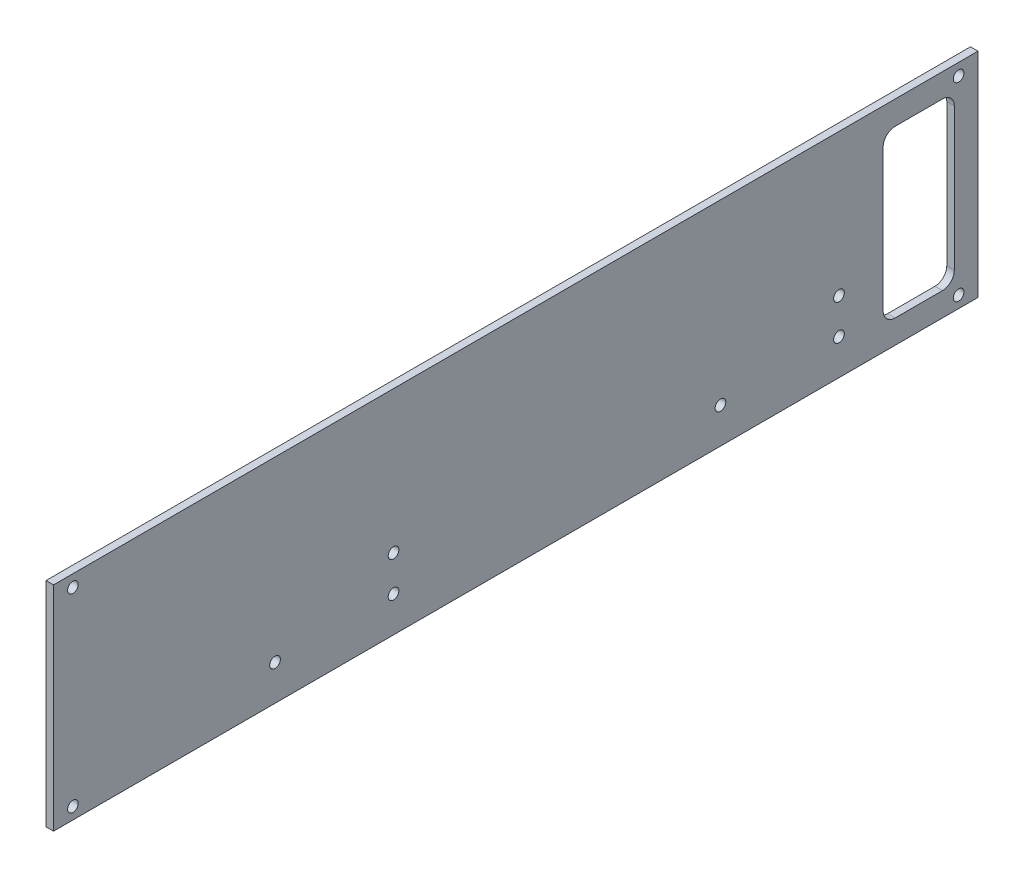
SolidWorks part; units mm, degrees
ref_plane "Front Plane" through (0, 0, 0) normal (0, 0, 1) x (1, 0, 0)
ref_plane "Top Plane" through (0, 0, 0) normal (0, 1, 0) x (1, 0, 0)
ref_plane "Right Plane" through (0, 0, 0) normal (1, 0, 0) x (0, 0, -1)
sketch "Sketch1" plane through (0, 0, 0) normal (1, 0, 0) x (0, 0, -1)
  line L1 (-195, -45) -> (195, -45)
  line L2 (-195, -45) -> (-195, 45)
  line L3 (-195, 45) -> (195, 45)
  line L4 (195, -45) -> (195, 45)
  line L5 (-195, -45) -> (195, 45) construction
  line L6 (-195, 45) -> (195, -45) construction
  point P0 (0, 0)
  dimension "D1" = 390
  dimension "D2" = 90
extrude "Boss-Extrude1" add sketch "Sketch1" along normal blind 3.175
hole_wizard "M4 Clearance Hole1" positions "Sketch2" profile "Sketch3" hole size "M4" standard "ANSI Metric" end condition through all
sketch "Sketch2" plane through (3.175, 0, 0) normal (1, 0, 0) x (0, 0, -1)
  line L0 (-178.884, -45) -> (-7.9152, 0.811)
  line L1 (-195, -45) -> (195, -45) construction
  line L2 (-7.9152, 0.811) -> (-20.8561, 49.1073)
  line L3 (-20.8561, 49.1073) -> (-191.825, 3.2963)
  line L4 (-191.825, 3.2963) -> (-178.884, -45)
  line L6 (9.0311, -45) -> (180, 0.811)
  line L7 (180, 0.811) -> (167.059, 49.1073)
  line L8 (167.059, 49.1073) -> (-3.9098, 3.2963)
  line L9 (-3.9098, 3.2963) -> (9.0311, -45)
  line L11 (-141.5635, -35) -> (-141.5635, -45)
  line L13 (46.3516, -45) -> (46.3516, -35)
  line L15 (195, -45) -> (195, 45) construction
  line L17 (-195, 45) -> (-195, -45) construction
  line L19 (-195, -45) -> (-181.825, -45)
  line L20 (-195, -45) -> (-195, -35)
  line L21 (-195, -35) -> (-181.825, -35)
  line L22 (-181.825, -45) -> (-181.825, -35)
  point P30 (-101.5635, -30)
  point P32 (-51.5635, -30)
  point P34 (-51.5635, -15)
  point P36 (86.3516, -30)
  point P38 (136.3516, -30)
  point P40 (136.3516, -15)
  dimension "D1" = 177
  dimension "D2" = 50
  dimension "D3" = 15
  dimension "D4" = 3.175
  dimension "D6" = 10
  dimension "D7" = 15
  dimension "D8" = 10
  dimension "D9" = 40
  dimension "D10" = 90
  dimension "D11" = 15
  dimension "D12" = 15
  dimension "D13" = 40
  dimension "D14" = 90
  dimension "D15" = 13.175
  dimension "D16" = 10
  dimension "D5" = 2
sketch "Sketch3" plane through (3.175, -15, -136.3516) normal (0, 1, 0) x (0, 0, -1)
  line L0 (0, 0) -> (0, 3.175)
  line L1 (0, 3.175) -> (2.25, 3.175)
  line L2 (2.25, 3.175) -> (2.25, 0)
  line L5 (2.25, 0) -> (0, 0)
  line L11 (0, -6.35) -> (0, 107.95) construction
  dimension "Thru Hole Dia." = 4.5
  dimension "Thru Hole Depth" = 3.175
sketch "Sketch4" plane through (3.175, 0, 0) normal (1, 0, 0) x (0, 0, -1)
  line L0 (195, -45) -> (195, 45) construction
  line L1 (155, -35) -> (185, -35)
  line L2 (155, -35) -> (155, 35)
  line L3 (155, 35) -> (185, 35)
  line L4 (185, -35) -> (185, 35)
  line L5 (155, -35) -> (185, 35) construction
  line L6 (155, 35) -> (185, -35) construction
  point P0 (170, 0)
  dimension "D1" = 30
  dimension "D2" = 70
  dimension "D3" = 10
extrude "Cut-Extrude1" cut sketch "Sketch4" against normal through all
fillet "Fillet1" radius 5 4 edges at (1.5875, 35, -185) (1.5875, 35, -155) (1.5875, -35, -155) (1.5875, -35, -185)
hole_wizard "M4 Clearance Hole2" positions "Sketch5" profile "Sketch6" hole size "M4" standard "ANSI Metric" end condition through all
sketch "Sketch5" plane through (3.175, 0, 0) normal (1, 0, 0) x (0, 0, -1)
  line L0 (-195, 45) -> (-195, -45) construction
  line L1 (-195, -45) -> (195, -45) construction
  point P0 (-186.825, -40)
  dimension "D1" = 8.175
  dimension "D2" = 5
sketch "Sketch6" plane through (3.175, -40, 186.825) normal (0, 1, 0) x (0, 0, -1)
  line L0 (0, 0) -> (0, 3.175)
  line L1 (0, 3.175) -> (2.25, 3.175)
  line L2 (2.25, 3.175) -> (2.25, 0)
  line L5 (2.25, 0) -> (0, 0)
  line L11 (0, -6.35) -> (0, 107.95) construction
  dimension "Thru Hole Dia." = 4.5
  dimension "Thru Hole Depth" = 3.175
mirror "Mirror1" about plane through (0, 0, 0) normal (0, 0, 1) of "M4 Clearance Hole2" second plane through (0, 0, 0) second plane normal (0, 1, 0)
